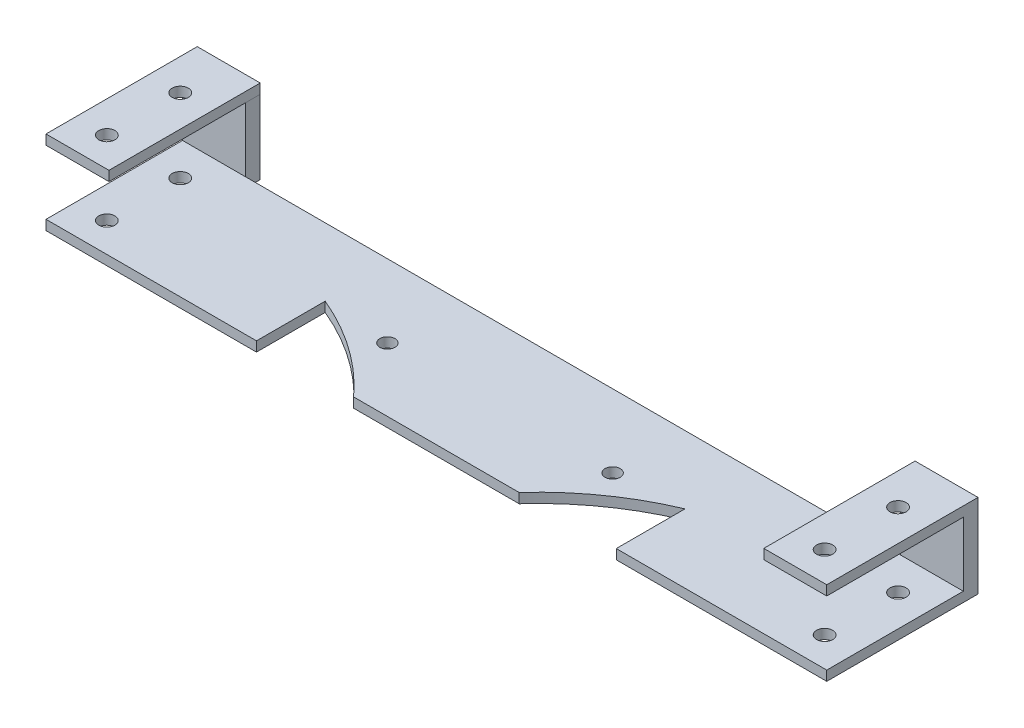
SolidWorks part; units mm, degrees
ref_plane "Front Plane" through (0, 0, 0) normal (0, 0, 1) x (1, 0, 0)
ref_plane "Top Plane" through (0, 0, 0) normal (0, 1, 0) x (1, 0, 0)
ref_plane "Right Plane" through (0, 0, 0) normal (1, 0, 0) x (0, 0, -1)
sketch "Sketch1" plane through (0, 0, 0) normal (0, 1, 0) x (1, 0, 0)
  line L0 (21.5, 65.3) -> (8.64, 65.3)
  line L1 (15.07, 58.4) -> (15.07, 43.4) construction
  line L2 (8.64, 65.3) -> (8.64, 37.4)
  line L3 (8.64, 37.4) -> (21.5, 37.4)
  line L4 (21.5, 37.4) -> (21.5, 65.3)
  line L5 (-55.75, 0) -> (55.75, 0) construction
  line L6 (8.64, 65.3) -> (8.64, 68.3)
  line L7 (8.64, 68.3) -> (21.5, 68.3)
  line L8 (21.5, 68.3) -> (21.5, 65.3)
  line L9 (138, 37.4) -> (138, 65.3)
  line L10 (138, 65.3) -> (125.14, 65.3)
  line L11 (125.14, 65.3) -> (125.14, 37.4)
  line L12 (125.14, 37.4) -> (138, 37.4)
  line L13 (125.14, 68.3) -> (138, 68.3)
  line L14 (125.14, 65.3) -> (125.14, 68.3)
  line L15 (138, 68.3) -> (138, 65.3)
  line L16 (60.75, 0) -> (172.25, 0) construction
  line L17 (21.5, 65.3) -> (125.14, 65.3)
  line L18 (21.5, 37.4) -> (125.14, 37.4)
  line L19 (0, 0) -> (0, 55.75) construction
  line L20 (-21.5, 65.3) -> (-8.64, 65.3)
  line L22 (-8.64, 37.4) -> (-21.5, 37.4)
  line L23 (-21.5, 37.4) -> (-21.5, 65.3)
  line L24 (-8.64, 65.3) -> (8.64, 65.3)
  line L25 (-8.64, 37.4) -> (8.64, 37.4)
  line L26 (-8.64, 65.3) -> (-8.64, 37.4)
  line L27 (-8.64, 65.3) -> (-8.64, 68.3)
  line L28 (-21.5, 68.3) -> (-21.5, 65.3)
  line L29 (-8.64, 68.3) -> (-21.5, 68.3)
  line L30 (60.75, 0) -> (55.75, 0) construction
  line L31 (58.25, 65.3) -> (58.25, -65.3) construction
  line L32 (21.5, 51.4375) -> (21.5, 37.4)
  line L33 (95, 37.4) -> (95, 51.4375)
  line L34 (95, 37.4) -> (75.1563, 37.4)
  line L35 (21.5, 37.4) -> (41.3437, 37.4)
  circle A0 centre (0, 0) radius 55.75 construction
  circle A1 centre (15.07, 43.4) radius 1.65
  circle A2 centre (15.07, 58.4) radius 1.65
  circle A3 centre (116.5, 0) radius 55.75 construction
  circle A4 centre (131.57, 43.4) radius 1.65
  circle A5 centre (131.57, 58.4) radius 1.65
  circle A6 centre (-15.07, 43.4) radius 1.65
  circle A7 centre (-15.07, 58.4) radius 1.65
  circle A8 centre (35.25, 50.4) radius 1.55
  circle A9 centre (81.25, 50.4) radius 1.55
  arc A10 (41.3437, 37.4) -> (21.5, 51.4375) centre (0, 0) ccw
  arc A11 (75.1563, 37.4) -> (95, 51.4375) centre (116.5, 0) cw
  point P3 (21.5, 65.3)
  point P6 (15.07, 65.3)
  point P13 (15.07, 37.4)
  point P46 (58.25, 0)
  point P52 (41.3437, 37.4)
  dimension "D1" = 111.5
  dimension "D5" = 3.3
  dimension "D8" = 6
  dimension "D12" = 3.1
  dimension "D2" = 21.5
  dimension "D3" = 65.3
  dimension "D4" = 12.86
  dimension "D6" = 21.9
  dimension "D7" = 15
  dimension "D9" = 3
  dimension "D11" = 5
  dimension "D13" = 23
  dimension "D14" = 13
  dimension "D10" = 2
extrude "Boss-Extrude1" add sketch "Sketch1" along normal blind 2 contours L3 L4 L0 L2 A2 A1 | L11 L12 L9 L10 A5 A4 | L15 L13 L14 L10 | L4 L18 L11 L17 | L22 L25 L2 L24 L20 L23 A6 A7 | A2 | A1 | L24 L26 L25 L2 | L27 L29 L28 L20 region at (15.07, 0, -51.3725) region at (75.3095, 0, -52.4773) region at (0, 0, -51.35) region at (131.57, 0, -66.8) region at (131.57, 0, -51.3725) region at (-15.07, 0, -51.3725) region at (-15.07, 0, -66.8) region at (15.07, 0, -43.4) region at (15.07, 0, -58.4)
extrude "Boss-Extrude2" add sketch "Sketch1<4>" along normal blind 2 from offset 15.1 separate body contours L11 L12 L9 L10 A5 A4 | L15 L13 L14 L10 | L27 L29 L28 L20 | L26 L20 L23 L22 A6 A7 region at (131.57, 0, -66.8) region at (131.57, 0, -51.3725) region at (-15.07, 0, -51.3725) region at (-15.07, 0, -66.8)
sketch "Sketch1<4>" plane through (0, 0, 0) normal (0, 1, 0) x (1, 0, 0) same geometry as "Sketch1"
extrude "Boss-Extrude3" add sketch "Sketch1<5>" along normal up to surface (15.1 mm away) contours L15 L13 L14 L10 | L27 L29 L28 L20 region at (131.57, 0, -66.8) region at (-15.07, 0, -66.8) up to face at (131.57, 15.1, -56.75)
sketch "Sketch1<5>" plane through (0, 0, 0) normal (0, 1, 0) x (1, 0, 0) same geometry as "Sketch1"
